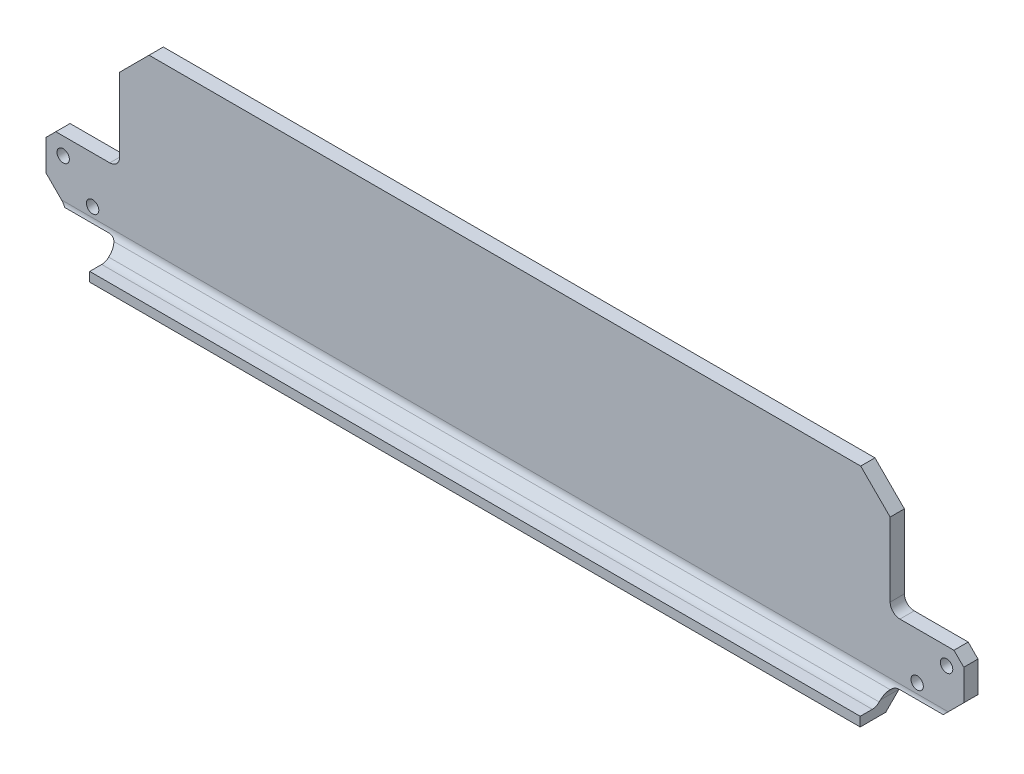
SolidWorks part; units mm, degrees
material "PLA"
ref_plane "Front Plane" through (0, 0, 0) normal (0, 0, 1) x (1, 0, 0)
ref_plane "Top Plane" through (0, 0, 0) normal (0, 1, 0) x (1, 0, 0)
ref_plane "Right Plane" through (0, 0, 0) normal (1, 0, 0) x (0, 0, -1)
sketch "Profile-Sketch" plane through (0, 0, 0) normal (0, 0, 1) x (1, 0, 0)
  line L0 (0, 0) -> (26895.2177, 0) construction
  line L1 (0, 0) -> (0, 26895.2177) construction
  line L2 (-114.3, 9.525) -> (-106.68, 9.525) construction
  line L3 (-114.3, 9.525) -> (-114.3, 17.145) construction
  circle A0 centre (-114.3, 9.525) radius 2 construction
  circle A1 centre (-106.68, 9.525) radius 1.6002 construction
  circle A2 centre (-114.3, 17.145) radius 1.6002 construction
  dimension "D3" = 4
  dimension "D4" = 3.2004
  dimension "D5" = 3.2004
  dimension "D1" = 9.525
  dimension "D2" = 114.3
  dimension "D6" = 7.62
  dimension "D7" = 7.62
sketch "Sketch2" plane through (0, 0, 0) normal (1, 0, 0) x (0, 0, -1)
  line L0 (0, 0) -> (50000, 0) construction
  line L1 (-11.43, 0) -> (-4.826, 0)
  line L2 (-4.826, 0) -> (0, 4.826)
  line L3 (0, -200000) -> (0, 226895.2177) construction
  line L4 (0, 4.826) -> (0, 50.8)
  line L5 (0, 11.525) -> (0, 7.525) construction
  line L6 (0, 50.8) -> (-3.683, 50.8)
  line L7 (-3.683, 50.8) -> (-3.683, 5.9923)
  line L8 (-3.683, 5.9923) -> (-7.2623, 2.413)
  line L9 (-7.2623, 2.413) -> (-11.43, 2.413)
  line L10 (-11.43, 2.413) -> (-11.43, 0)
  dimension "D1" = 3.683
  dimension "D2" = 50.8
  dimension "D3" = 3.429
  dimension "D4" = 2.413
  dimension "D5" = 45
  dimension "D6" = 11.43
  dimension "D7" = 4.826
extrude "Boss-Extrude1" add sketch "Sketch2" along normal mid plane 199.39
sketch "Sketch3" plane through (0, 0, 0) normal (0, 0, 1) x (1, 0, 0)
  line L0 (-99.695, 21.59) -> (-118.745, 21.59)
  line L1 (-99.695, 50.8) -> (-99.695, 5.9923) construction
  line L2 (-118.745, 21.59) -> (-118.745, 5.9923)
  line L3 (-118.745, 5.9923) -> (-99.695, 5.9923)
  line L4 (-200000, 0) -> (226895.2177, 0) construction
  line L5 (-99.695, 21.59) -> (-99.695, 5.9923)
  circle A0 centre (-114.3, 17.145) radius 1.6002 construction
  circle A1 centre (-106.68, 9.525) radius 1.6002 construction
  circle A2 centre (-114.3, 17.145) radius 1.6002
  circle A3 centre (-106.68, 9.525) radius 1.6002
  dimension "D2" = 21.59
  dimension "D3" = 19.05
extrude "Mounting-Plate" add sketch "Sketch3" along normal up to surface (3.683 mm away) up to face at (0, 28.3962, 3.683)
mirror "Mirror1" about plane through (0, 0, 0) normal (1, 0, 0) of "Mounting-Plate"
chamfer "Chamfer1" distance 5.08 angle 45 2 edges at (118.745, 5.9923, 1.8415) (-118.745, 5.9923, 1.8415)
chamfer "Chamfer2" distance 2.54 angle 45 2 edges at (118.745, 21.59, 1.8415) (-118.745, 21.59, 1.8415)
chamfer "Chamfer3" distance 7.62 angle 45 2 edges at (99.695, 50.8, 1.8415) (-99.695, 50.8, 1.8415)
fillet "Fillet1" radius 2.54 4 edges at (-99.695, 5.9923, 1.8415) (99.695, 5.9923, 1.8415) (99.695, 21.59, 1.8415) (-99.695, 21.59, 1.8415)
fillet "Fillet2" radius 2.54 2 edges at (0, 2.413, 7.2623) (0, 5.9923, 3.683)
